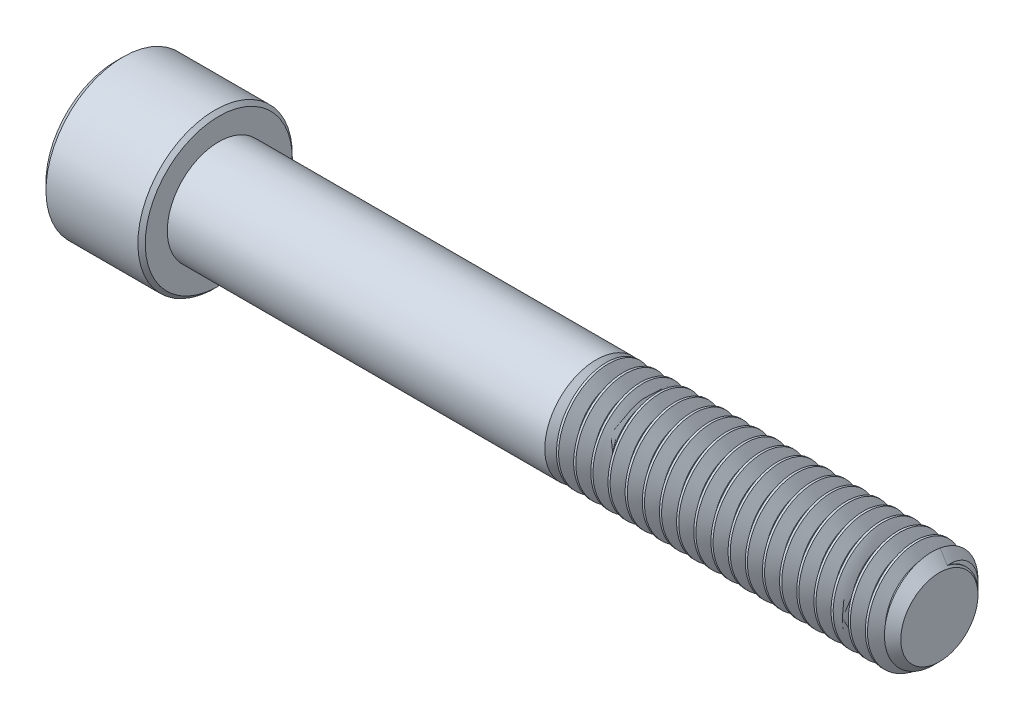
SolidWorks part; units mm, degrees
ref_plane "Front Plane" through (0, 0, 0) normal (0, 0, 1) x (1, 0, 0)
ref_plane "Top Plane" through (0, 0, 0) normal (0, 1, 0) x (1, 0, 0)
ref_plane "Right Plane" through (0, 0, 0) normal (1, 0, 0) x (0, 0, -1)
sketch "Sketch1" plane through (0, 0, 0) normal (0, 0, 1) x (1, 0, 0)
  line L0 (33.3375, 0) -> (-33.3375, 0) construction
  line L1 (33.3375, 4.7625) -> (33.3375, -4.7625) construction
  line L2 (-33.3375, 6.8036) -> (-33.3375, -6.8036) construction
  line L3 (-33.6777, 7.1437) -> (-42.1821, 7.1437) construction
  line L4 (-42.1821, 7.1437) -> (-42.8625, 6.4634) construction
  line L5 (-42.8625, 6.4634) -> (-42.8625, -6.4634) construction
  line L6 (-42.8625, -6.4634) -> (-42.1821, -7.1438) construction
  line L7 (-42.1821, -7.1438) -> (-33.6777, -7.1438) construction
  line L8 (1.5875, 4.7625) -> (1.5875, -4.7625) construction
  line L9 (-33.6777, 7.1437) -> (-33.3375, 6.8036) construction
  line L10 (-33.3375, -6.8036) -> (-33.6777, -7.1438) construction
  point P5 (-33.3375, 7.1437)
  point P6 (-33.3375, -7.1438)
  point P7 (-38.2397, 0)
  point P12 (26.9875, -4.7625)
  dimension "D1" = 45
  dimension "Dec." = 9.525
  dimension "Length" = 66.675
  dimension "Head Dia" = 14.2875
  dimension "Head Height" = 9.525
  dimension "Hex Depth" = 4.6228
  dimension "Chamfer" = 0.6804
  dimension "D2" = 6.35
  dimension "Thread Length" = 31.75
  dimension "D3" = 0.3402
  dimension "D4" = 45
ref_plane "Plane1" through (33.3375, 0, 0) normal (1, 0, 0) x (0, 0, -1)
ref_plane "Plane2" through (-42.8625, 0, 0) normal (1, 0, 0) x (0, 0, -1)
sketch "Sketch2" plane through (33.3375, 0, 0) normal (1, 0, 0) x (0, 0, -1)
  circle A0 centre (0, 0) radius 4.7625
extrude "Boss-Extrude1" add sketch "Sketch2" against normal up to vertex (31.75 mm away) up to point (1.5875, 4.7625, 0)
sketch "Sketch3" plane through (33.3375, 0, 0) normal (1, 0, 0) x (0, 0, -1)
  circle A0 centre (0, 0) radius 4.7625 construction
  circle A1 centre (0, 0) radius 4.7625
curve "Helix/Spiral1" pitch 1.5875 height 33.3375 radius 4.7625 centre (33.3375, 0, 0) axis (-1, 0, 0) start towards (0, 1, 0) parameters "Pitch"=1.5875
chamfer "Chamfer1" distance 1.1906 angle 45 1 edges at (33.3375, 0, -4.7625)
sketch "Sketch5" plane through (0, 0, 0) normal (0, 0, 1) x (1, 0, 0)
  line L0 (32.643, 4.7625) -> (34.032, 4.7625)
  line L1 (34.032, 4.7625) -> (33.4367, 3.7314)
  line L2 (33.4367, 3.7314) -> (33.2383, 3.7314)
  line L3 (33.2383, 3.7314) -> (32.643, 4.7625)
  line L4 (33.3375, 3.7314) -> (33.3375, 4.7625) construction
  line L5 (32.9406, 4.2469) -> (33.7344, 4.2469) construction
  dimension "D1" = 60
  dimension "D2" = 0.7937
  dimension "D3" = 0.1984
sweep "Cut-Sweep1" cut profiles "Sketch5" path "Helix/Spiral1" align with end faces yes
sketch "Sketch4" plane through (-42.8625, 0, 0) normal (1, 0, 0) x (0, 0, -1)
  line L0 (-7.1437, 0.7937) -> (7.1437, 0.7937) construction
  line L1 (0, 4.5827) -> (-3.9688, 2.2914)
  line L2 (-3.9688, 2.2914) -> (-3.9688, -2.2914)
  line L3 (-3.9688, -2.2914) -> (0, -4.5827)
  line L4 (0, -4.5827) -> (3.9688, -2.2914)
  line L5 (3.9688, -2.2914) -> (3.9688, 2.2914)
  line L6 (3.9688, 2.2914) -> (0, 4.5827)
  line L7 (0, 0) -> (0, 0.7937) construction
  circle A0 centre (0, 0) radius 3.9688 construction
  dimension "D2" = 0.7937
  dimension "Hex Size" = 7.9375
  dimension "D1" = 14.2875
sketch "Sketch10" plane through (0, 0, 0) normal (0, 0, 1) x (1, 0, 0)
  line L0 (-33.3375, 0) -> (-33.3375, 4.7625)
  line L1 (-33.3375, 6.8036) -> (-33.3375, -6.8036) construction
  line L2 (-33.3375, 4.7625) -> (1.5875, 4.7625)
  line L3 (1.5875, 4.7625) -> (6.35, 0)
  line L4 (33.3375, 0) -> (-33.3375, 0) construction
  line L5 (-33.3375, 0) -> (6.35, 0) construction
  line L6 (-33.3375, 0) -> (6.35, 0)
  dimension "D1" = 45
revolve "Revolve2" add sketch "Sketch10" angle 360 about L5
sketch "Sketch6" plane through (0, 0, 0) normal (0, 0, 1) x (1, 0, 0)
  line L0 (-42.1821, 7.1437) -> (-42.8625, 6.4634) construction
  line L2 (-33.3375, 6.8036) -> (-33.3375, -6.8036) construction
  line L3 (-42.8625, 6.4634) -> (-42.8625, -6.4634) construction
  line L4 (-42.1821, 7.1437) -> (-42.8625, 6.4634)
  line L5 (-33.6777, 7.1437) -> (-42.1821, 7.1437) construction
  line L6 (-33.3375, 6.8036) -> (-33.3375, 0)
  line L7 (-42.8625, 6.4634) -> (-42.8625, 0)
  line L8 (-33.3375, 0) -> (-42.8625, 0) construction
  line L9 (-33.3375, 0) -> (-42.8625, 0)
  line L10 (-33.6777, 7.1437) -> (-33.3375, 6.8036) construction
  line L11 (-33.6777, 7.1437) -> (-42.1821, 7.1437)
  line L12 (-33.6777, 7.1437) -> (-33.3375, 6.8036)
revolve "Revolve1" add sketch "Sketch6" angle 360 about L8
extrude "Cut-Extrude1" cut sketch "Sketch4" along normal up to vertex (4.6228 mm away) up to point (-38.2397, 0, 0)
sketch "Sketch8" plane through (-42.8625, 0, 0) normal (-1, 0, 0) x (0, 0, 1)
  circle A1 centre (0, 0) radius 4.5827
extrude "Cut-Extrude2" cut sketch "Sketch8" against normal blind 1.3607 draft 45
equation "\"D3@Helix/Spiral1\" = \"Thread Length@Sketch1\"+\"Pitch@Helix/Spiral1\""
equation "\"D3@Sketch5\" = \"Pitch@Helix/Spiral1\"*.125"
equation "\"D2@Sketch5\" = \"Pitch@Helix/Spiral1\"*.50"
equation "\"D1@Chamfer1\" = \"Pitch@Helix/Spiral1\"*.75"
equation "\"D2@Sketch1\" = \"Pitch@Helix/Spiral1\"*4"
equation "\"D1@Sketch4\" = \"Head Dia@Sketch1\""
equation "\"Chamfer@Sketch1\" = \"Head Height@Sketch1\"/14"
equation "\"D3@Sketch1\" = \"Chamfer@Sketch1\"*.50"
equation "\"D1@Cut-Extrude2\" = \"Chamfer@Sketch1\"*2"
